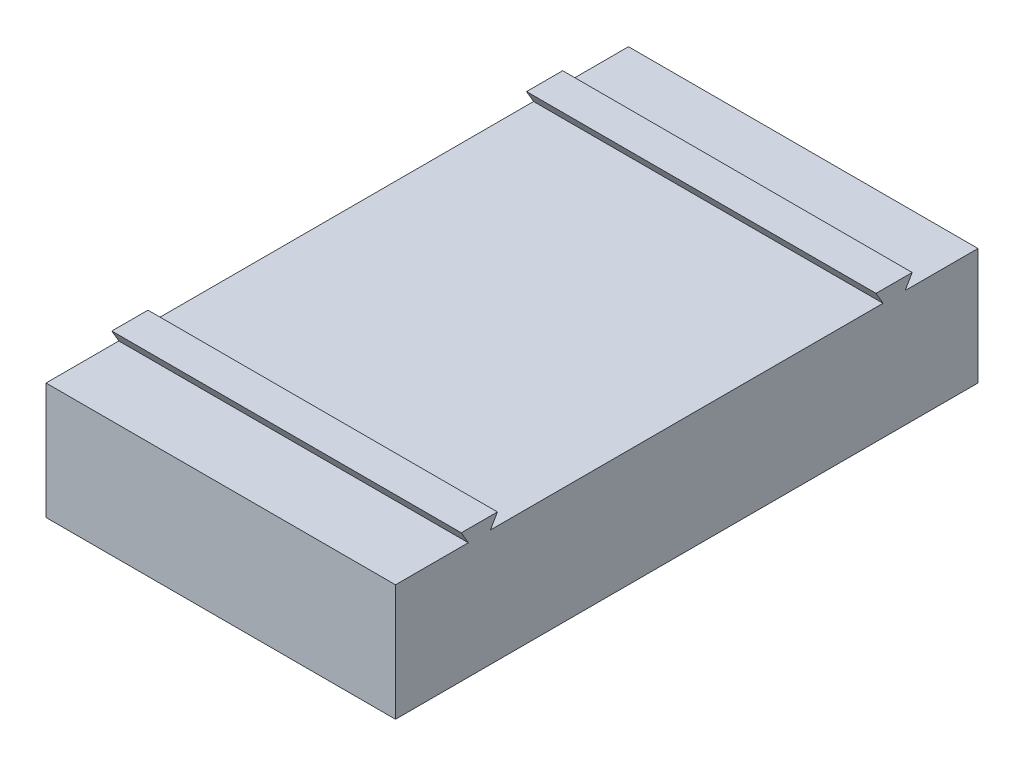
SolidWorks part; units mm, degrees
ref_plane "Front Plane" through (0, 0, 0) normal (0, 0, 1) x (1, 0, 0)
ref_plane "Top Plane" through (0, 0, 0) normal (0, 1, 0) x (1, 0, 0)
ref_plane "Right Plane" through (0, 0, 0) normal (1, 0, 0) x (0, 0, -1)
sketch "Sketch1" plane through (0, 0, 0) normal (0, 1, 0) x (1, 0, 0)
  line L1 (60, -100) -> (-60, -100)
  line L2 (60, -100) -> (60, 100)
  line L3 (60, 100) -> (-60, 100)
  line L4 (-60, -100) -> (-60, 100)
  line L5 (60, -100) -> (-60, 100) construction
  line L6 (60, 100) -> (-60, -100) construction
  point P0 (0, 0)
  dimension "D1" = 120
  dimension "D2" = 200
extrude "Boss-Extrude1" add sketch "Sketch1" along normal blind 40
ref_point "Point1"
ref_axis "Axis1" through (0, 0, 0) along (0, 1, 0)
ref_point "Point2"
ref_axis "Axis2" through (-60, 20, 0) along (1, 0, 0)
ref_point "CM"
sketch "Sketch2" plane through (60, 0, 0) normal (1, 0, 0) x (0, 0, -1)
  line L0 (67.4, 40) -> (64.9982, 44.16)
  line L1 (-100, 40) -> (100, 40) construction
  line L2 (64.9982, 44.16) -> (77.4018, 44.16)
  line L3 (77.4018, 44.16) -> (75, 40)
  line L4 (75, 40) -> (67.4, 40)
  line L5 (0, -1000) -> (0, 49000) construction
  line L6 (100, 40) -> (100, 0) construction
  line L7 (-75, 40) -> (-77.4018, 44.16)
  line L8 (-77.4018, 44.16) -> (-64.9982, 44.16)
  line L9 (-64.9982, 44.16) -> (-67.4, 40)
  line L10 (-67.4, 40) -> (-75, 40)
  line L11 (-100, 40) -> (-100, 0) construction
  dimension "D1" = 60
  dimension "D2" = 4.16
  dimension "D3" = 60
  dimension "D4" = 7.6
  dimension "D5" = 25
  dimension "D6" = 60
  dimension "D7" = 60
  dimension "D8" = 7.6
  dimension "D9" = 4.16
  dimension "D10" = 25
extrude "Boss-Extrude2" add sketch "Sketch2" against normal up to surface (120 mm away) up to face at (-60, 20, 0)
sketch "Sketch3" plane through (0, 0, 0) normal (0, -1, 0) x (1, 0, 0)
  line L0 (-60, 100) -> (60, 100) construction
  line L1 (56, -96) -> (-56, -96)
  line L2 (56, -96) -> (56, 96)
  line L3 (56, 96) -> (-56, 96)
  line L4 (-56, -96) -> (-56, 96)
  line L5 (56, -96) -> (-56, 96) construction
  line L6 (56, 96) -> (-56, -96) construction
  line L7 (60, 100) -> (60, -100) construction
  point P0 (0, 0)
  dimension "D1" = 4
  dimension "D2" = 4
sketch "Sketch5" plane through (0, 0, 0) normal (0, -1, 0) x (1, 0, 0)
  line L0 (-10.8887, -30.1351) -> (-10.8887, 13.3244)
  line L1 (-10.8887, 13.3244) -> (-25.4837, 13.3244)
  line L2 (-25.4837, 13.3244) -> (0, 40.5462)
  line L3 (0, 40.5462) -> (25.4837, 13.3244)
  line L4 (25.4837, 13.3244) -> (10.8887, 13.3244)
  line L5 (10.8887, 13.3244) -> (10.8887, -30.1351)
  line L6 (10.8887, -30.1351) -> (-10.8887, -30.1351)
  line L7 (0, -990.9816) -> (0, 49009.0184) construction
  line L8 (56, -96) -> (-56, 96) construction
  point P12 (0, 0)
extrude "Cut-Extrude2" cut sketch "Sketch5" against normal blind 1
